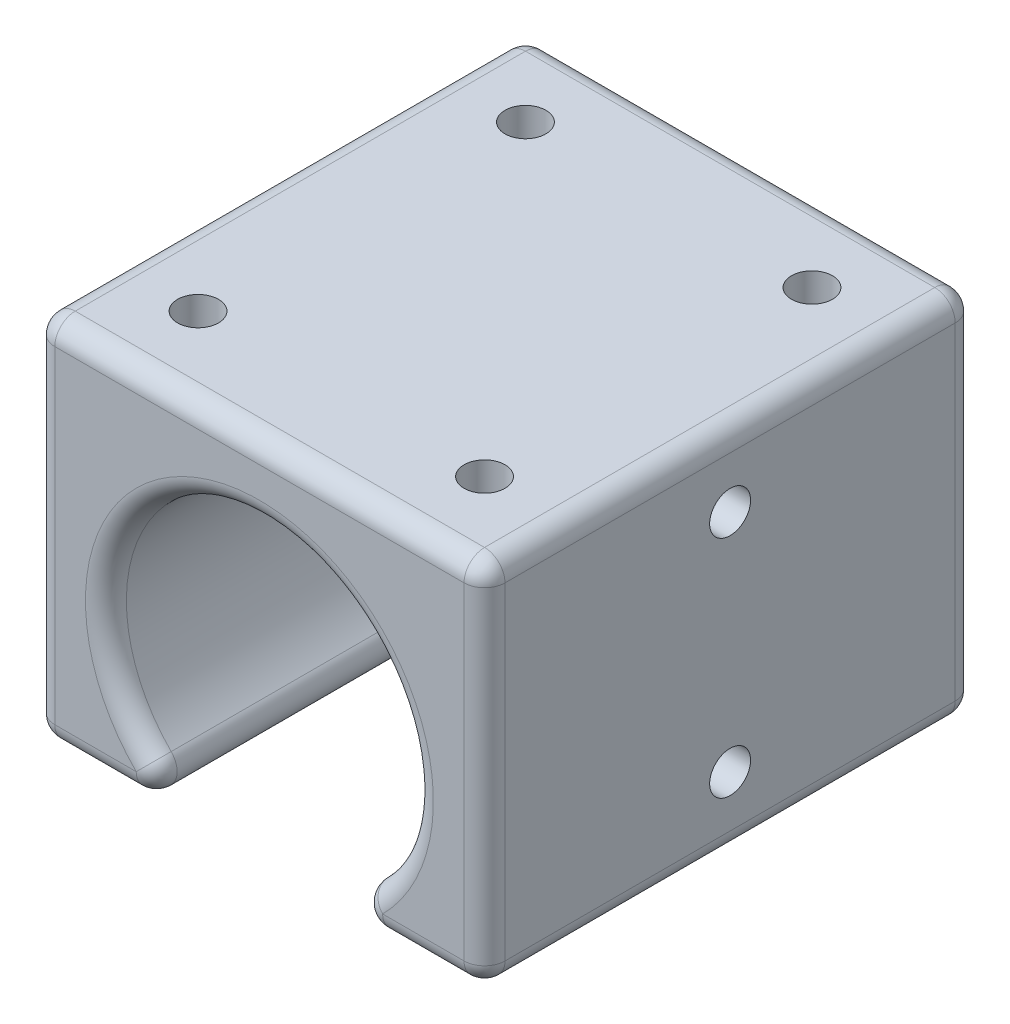
SolidWorks part; units mm, degrees
material "Alliage 1060"
ref_plane "Plan de face" through (0, 0, 0) normal (0, 0, 1) x (1, 0, 0)
ref_plane "Plan de dessus" through (0, 0, 0) normal (0, 1, 0) x (1, 0, 0)
ref_plane "Plan de droite" through (0, 0, 0) normal (1, 0, 0) x (0, 0, -1)
sketch "Esquisse1" plane through (0, 0, 0) normal (0, 0, 1) x (1, 0, 0)
  line L0 (0, 0) -> (0, -2) construction
  line L1 (11, -9) -> (2.6926, -9)
  line L2 (11, -9) -> (11, 9)
  line L3 (11, 9) -> (-11, 9)
  line L4 (-11, -9) -> (-11, 9)
  line L5 (11, -9) -> (-11, 9) construction
  line L6 (11, 9) -> (-11, -9) construction
  line L7 (2.6926, -9) -> (-2.6926, -9) construction
  line L8 (-2.6926, -9) -> (-11, -9)
  arc A1 (2.6926, -9) -> (-2.6926, -9) centre (0, -2) ccw
  arc A2 (-2.6926, -9) -> (2.6926, -9) centre (0, -2) ccw construction
  point P0 (0, 0)
  dimension "D2" = 2
  dimension "D4" = 15
  dimension "D1" = 11
  dimension "D3" = 11
extrude "Boss.-Extru.1" add sketch "Esquisse1" along normal blind 12 and the other way blind 12
sketch "Esquisse2" plane through (0, 0, 0) normal (0, 1, 0) x (1, 0, 0)
  line L0 (11, 12) -> (-11, 12) construction
  line L1 (7, -8) -> (-7, -8) construction
  line L2 (7, -8) -> (7, 8) construction
  line L3 (7, 8) -> (-7, 8) construction
  line L4 (-7, -8) -> (-7, 8) construction
  line L5 (7, -8) -> (-7, 8) construction
  line L6 (7, 8) -> (-7, -8) construction
  line L7 (-11, 12) -> (-11, -12) construction
  circle A0 centre (-7, 8) radius 1
  circle A1 centre (7, 8) radius 1
  circle A2 centre (7, -8) radius 1
  circle A3 centre (-7, -8) radius 1
  point P0 (0, 0)
  dimension "D3" = 2
  dimension "D4" = 2
  dimension "D5" = 2
  dimension "D6" = 2
  dimension "D1" = 14
  dimension "D2" = 16
extrude "Enlèv. mat.-Extru.1" cut sketch "Esquisse2" against normal blind 4 from surface starting at face at (0, 9, 0)
fillet "Congé1" radius 1 18 edges at (-11, 9, 0) (-11, -9, 0) (-6.8463, -9, -12) (0, 5.5, -12) (6.8463, -9, -12) (0, 9, -12) (-11, 0, -12) (11, 0, -12) (11, -9, 0) (11, 9, 0) (0, 9, 12) (11, 0, 12) (6.8463, -9, 12) (0, 5.5, 12) (-6.8463, -9, 12) (-11, 0, 12) (2.6926, -9, 0) (-2.6926, -9, 0)
sketch "Esquisse3" plane through (-11, 0, 0) normal (-1, 0, 0) x (0, 0, 1)
  line L0 (0, 5.5) -> (0, -5.5) construction
  circle A0 centre (0, 5.5) radius 1
  circle A1 centre (0, -5.5) radius 1
  dimension "D2" = 2
  dimension "D1" = 11
extrude "Enlèv. mat.-Extru.2" cut sketch "Esquisse3" against normal blind 2.5
sketch "Esquisse6" plane through (11, 0, 0) normal (1, 0, 0) x (0, 0, -1)
  line L5 (0, -5.5) -> (0, 5.5) construction
  circle A0 centre (0, 5.5) radius 1
  circle A1 centre (0, -5.5) radius 1
  dimension "D2" = 2
  dimension "D1" = 11
extrude "Enlèv. mat.-Extru.4" cut sketch "Esquisse6" against normal blind 2.5
